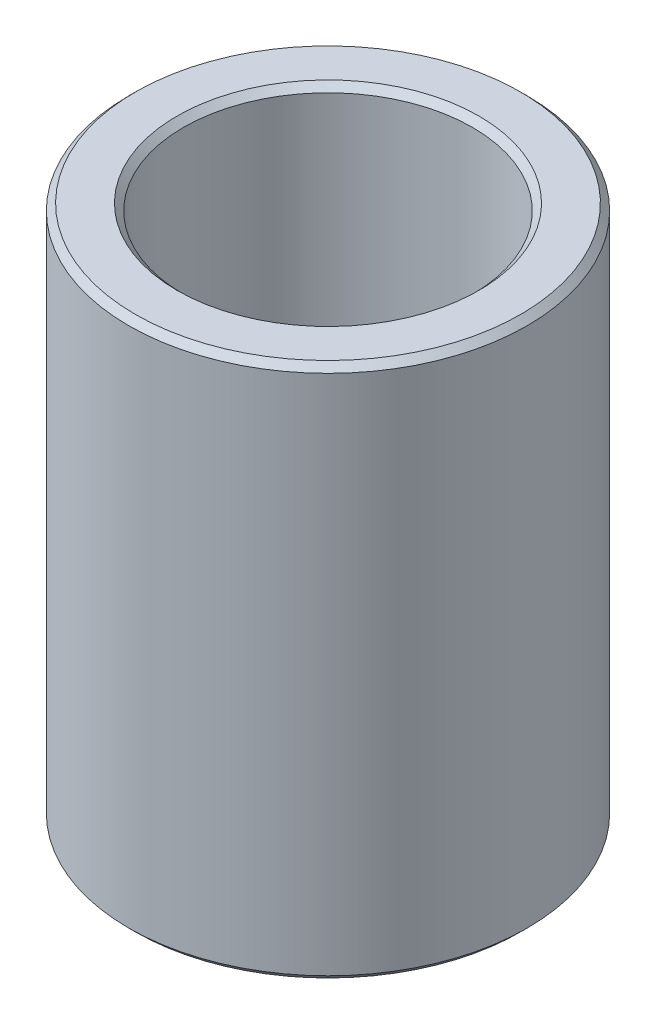
SolidWorks part; units mm, degrees
ref_plane "Front Plane" through (0, 0, 0) normal (0, 0, 1) x (1, 0, 0)
ref_plane "Top Plane" through (0, 0, 0) normal (0, 1, 0) x (1, 0, 0)
ref_plane "Right Plane" through (0, 0, 0) normal (1, 0, 0) x (0, 0, -1)
sketch "Sketch1" plane through (0, 0, 0) normal (0, 1, 0) x (1, 0, 0)
  circle A0 centre (0, 0) radius 42.5
  dimension "SLEEVE_OD" = 85
extrude "Boss-Extrude1" add sketch "Sketch1" along normal blind 114.1137
sketch "Sketch2" plane through (0, 0, 0) normal (0, 1, 0) x (1, 0, 0)
  circle A0 centre (0, 0) radius 30.8314
  dimension "BORE_D" = 61.6627
extrude "Cut-Extrude1" cut sketch "Sketch2" along normal through all
chamfer "Chamfer1" distance 1.3926 angle 45 4 edges at (0, 114.1137, 30.8314) (0, 0, 30.8314) (0, 0, 42.5) (0, 114.1137, 42.5)
